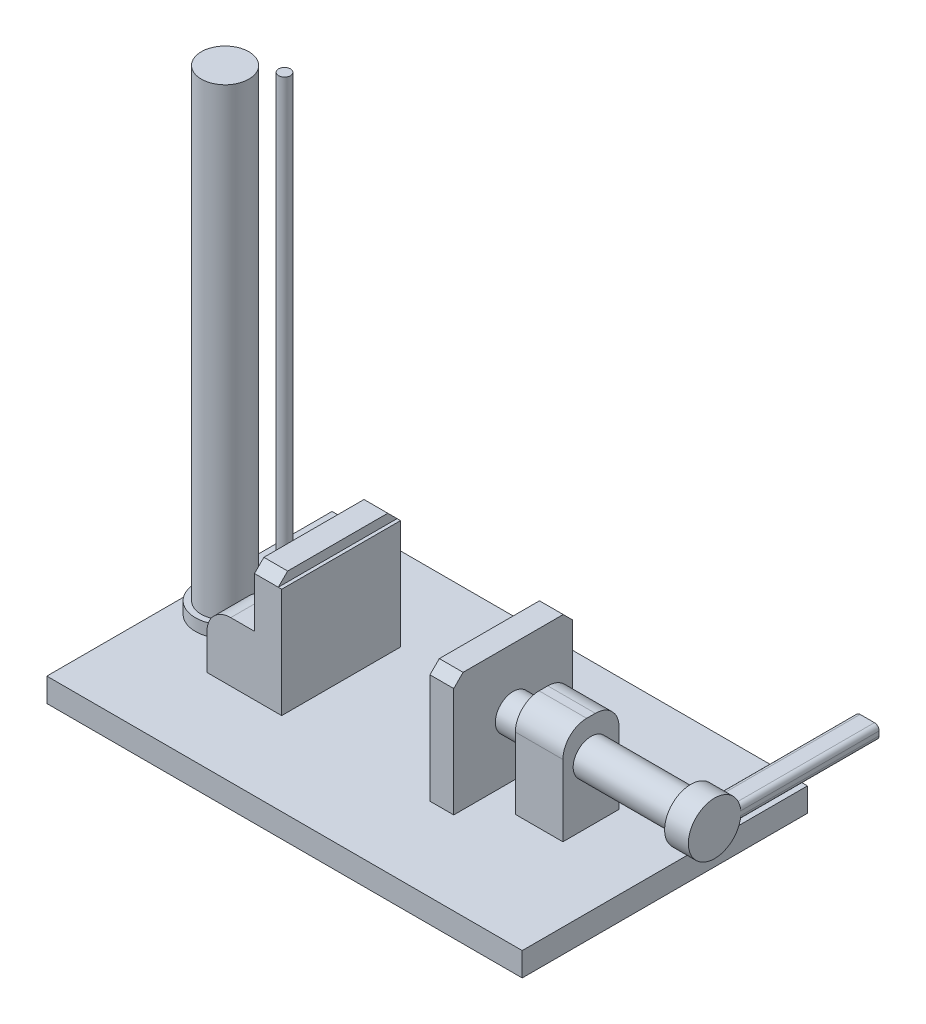
SolidWorks part; units mm, degrees
ref_plane "Front Plane" through (0, 0, 0) normal (0, 0, 1) x (1, 0, 0)
ref_plane "Top Plane" through (0, 0, 0) normal (0, 1, 0) x (1, 0, 0)
ref_plane "Right Plane" through (0, 0, 0) normal (1, 0, 0) x (0, 0, -1)
sketch "Sketch1" plane through (0, 0, 0) normal (0, 1, 0) x (1, 0, 0)
  line L1 (-254, 152.4) -> (254, 152.4)
  line L2 (-254, 152.4) -> (-254, -152.4)
  line L3 (-254, -152.4) -> (254, -152.4)
  line L4 (254, 152.4) -> (254, -152.4)
  line L5 (-254, 152.4) -> (254, -152.4) construction
  line L6 (-254, -152.4) -> (254, 152.4) construction
  point P0 (0, 0)
  dimension "D1" = 508
  dimension "D2" = 304.8
extrude "Boss-Extrude1" add sketch "Sketch1" along normal blind 25.4
sketch "Sketch2" plane through (0, 25.4, 0) normal (0, 1, 0) x (1, 0, 0)
  line L0 (-254, 152.4) -> (-177.8, 152.4)
  line L1 (254, 152.4) -> (-254, 152.4) construction
  line L2 (-215.9, 152.4) -> (-215.9, 25.4)
  line L3 (-254, -152.4) -> (254, -152.4) construction
  line L4 (-215.9, -25.4) -> (-215.9, -152.4)
  circle A0 centre (-215.9, 0) radius 25.4
  line M3 (-254, 152.4) -> (-254, -152.4)
  dimension "D2" = 50.8
  dimension "D1" = 76.2
extrude "Boss-Extrude2" add sketch "Sketch2" along normal blind 508 contours A0 M3 region at (-215.9, 25.4, 0)
sketch "Sketch3" plane through (0, 25.4, 0) normal (0, 1, 0) x (1, 0, 0)
  circle A0 centre (-215.9, 0) radius 31.75
  dimension "D1" = 63.5
extrude "Boss-Extrude3" add sketch "Sketch3" along normal blind 12.7
sketch "Sketch4" plane through (0, 25.4, 0) normal (0, 1, 0) x (1, 0, 0)
  line L0 (-215.9, 0) -> (-152.4, 0)
  circle A0 centre (-152.4, 0) radius 6.35
  dimension "D2" = 12.7
  dimension "D1" = 63.5
extrude "Boss-Extrude4" add sketch "Sketch4" along normal blind 533.4 contours A0 region at (-152.4, 25.4, 6.1704)
sketch "Sketch5" plane through (0, 25.4, 0) normal (0, 1, 0) x (1, 0, 0)
  line L0 (-215.9, 0) -> (-120.9596, 0)
  line L1 (-120.9596, 63.5) -> (-120.9596, -63.5)
  line L2 (-146.3596, 63.5) -> (-95.5596, 63.5)
  line L3 (-146.3596, 63.5) -> (-146.3596, -63.5)
  line L4 (-146.3596, -63.5) -> (-95.5596, -63.5)
  line L5 (-95.5596, 63.5) -> (-95.5596, -63.5)
  line L6 (-146.3596, 63.5) -> (-95.5596, -63.5) construction
  line L7 (-146.3596, -63.5) -> (-95.5596, 63.5) construction
  dimension "D1" = 50.8
  dimension "D2" = 127
extrude "Boss-Extrude5" add sketch "Sketch5" along normal blind 127 contours L5 L2 L1 L4 region at (-108.2596, 25.4, 0)
sketch "Sketch6" plane through (0, 25.4, 0) normal (0, 1, 0) x (1, 0, 0)
  line L1 (-120.9596, 63.5) -> (-171.7596, 63.5)
  line L2 (-120.9596, 63.5) -> (-120.9596, 25.4)
  line L3 (-120.9596, 25.4) -> (-171.7596, 25.4)
  line L4 (-171.7596, 63.5) -> (-171.7596, 25.4)
  line L5 (-120.9596, -63.5) -> (-171.7596, -63.5)
  line L6 (-120.9596, -63.5) -> (-120.9596, -25.4)
  line L7 (-120.9596, -25.4) -> (-171.7596, -25.4)
  line L8 (-171.7596, -63.5) -> (-171.7596, -25.4)
  dimension "D1" = 50.8
  dimension "D2" = 50.8
  dimension "D3" = 38.1
  dimension "D4" = 38.1
extrude "Boss-Extrude6" add sketch "Sketch6" along normal blind 63.5
fillet "Fillet2" radius 25.4 2 edges at (-171.7596, 88.9, -44.45) (-171.7596, 88.9, 44.45)
sketch "Sketch7" plane through (0, 25.4, 0) normal (0, 1, 0) x (1, 0, 0)
  line L0 (-95.5596, 0) -> (254, 0)
  line L1 (-95.5596, 63.5) -> (-95.5596, -63.5) construction
  line L2 (254, -152.4) -> (254, 152.4) construction
  line L4 (66.5202, 63.5) -> (91.9202, 63.5)
  line L5 (66.5202, 63.5) -> (66.5202, -63.5)
  line L6 (66.5202, -63.5) -> (91.9202, -63.5)
  line L7 (91.9202, 63.5) -> (91.9202, -63.5)
  line L8 (66.5202, 63.5) -> (91.9202, -63.5) construction
  line L9 (66.5202, -63.5) -> (91.9202, 63.5) construction
  point P6 (79.2202, 0)
  dimension "D1" = 127
  dimension "D2" = 25.4
extrude "Boss-Extrude7" add sketch "Sketch7" along normal blind 127 contours L7 L6 L5 L4
sketch "Sketch8" plane through (0, 25.4, 0) normal (0, 1, 0) x (1, 0, 0)
  line L1 (124.2964, 30.0313) -> (175.0964, 30.0313)
  line L2 (124.2964, 30.0313) -> (124.2964, -30.0313)
  line L3 (124.2964, -30.0313) -> (175.0964, -30.0313)
  line L4 (175.0964, 30.0313) -> (175.0964, -30.0313)
  line L5 (124.2964, 30.0313) -> (175.0964, -30.0313) construction
  line L6 (124.2964, -30.0313) -> (175.0964, 30.0313) construction
  point P0 (149.6964, 0)
  dimension "D1" = 50.8
  dimension "D2" = 60.0627
extrude "Boss-Extrude9" add sketch "Sketch8" along normal blind 101.6
sketch "Sketch10" plane through (175.0964, 0, 0) normal (1, 0, 0) x (0, 0, -1)
  line L0 (-63.5, 88.9) -> (63.5, 88.9)
  line L1 (-63.5, 152.4) -> (-63.5, 25.4) construction
  line L2 (63.5, 152.4) -> (63.5, 25.4) construction
  circle A0 centre (0, 88.9) radius 19.05
  dimension "D1" = 38.1
extrude "Boss-Extrude10" add sketch "Sketch10" along normal mid plane 213.36 contours L0 A0 | A0 region at (175.0964, 96.9851, 0)
sketch "Sketch11" plane through (281.7764, 0, 0) normal (1, 0, 0) x (0, 0, -1)
  line L0 (19.05, 88.9) -> (145.9979, 88.9)
  line L2 (-10.8194, 96.2269) -> (175.8673, 96.2269)
  line L3 (-10.8194, 96.2269) -> (-10.8194, 81.5731)
  line L4 (-10.8194, 81.5731) -> (175.8673, 81.5731)
  line L5 (175.8673, 96.2269) -> (175.8673, 81.5731)
  line L6 (-10.8194, 96.2269) -> (175.8673, 81.5731) construction
  line L7 (-10.8194, 81.5731) -> (175.8673, 96.2269) construction
  circle A0 centre (0, 88.9) radius 19.05 construction
  circle A1 centre (0, 88.9) radius 19.05 construction
  point P7 (82.5239, 88.9)
extrude "Boss-Extrude11" add sketch "Sketch11" along normal blind 25.4 contours L3 L2 L5 L4
fillet "Fillet4" radius 5.08 4 edges at (307.1764, 81.5731, -82.5239) (281.7764, 81.5731, -96.7259) (307.1764, 96.2269, -82.5239) (281.7764, 96.2269, -96.7259)
sketch "Sketch12" plane through (281.7764, 0, 0) normal (1, 0, 0) x (0, 0, -1)
  line L0 (0, 107.95) -> (0, 69.85)
  circle A0 centre (0, 88.9) radius 19.05 construction
  arc A1 (17.5846, 96.2269) -> (17.5846, 81.5731) centre (0, 88.9) ccw construction
  circle A2 centre (0, 88.9) radius 28.0363
extrude "Boss-Extrude12" add sketch "Sketch12" along normal blind 25.4 contours A2
fillet "Fillet6" radius 25.4 2 edges at (149.6964, 127, -30.0313) (149.6964, 127, 30.0313)
chamfer "Chamfer1" distance 10 angle 45 4 edges at (-108.2596, 152.4, 63.5) (-108.2596, 152.4, -63.5) (79.2202, 152.4, -63.5) (79.2202, 152.4, 63.5)
sketch "Sketch13" plane through (-95.5596, 0, 0) normal (1, 0, 0) x (0, 0, -1)
  line L1 (-63.5, 25.4) -> (63.5, 25.4)
  line L2 (-63.5, 25.4) -> (-63.5, 142.4)
  line L3 (-63.5, 142.4) -> (63.5, 142.4)
  line L4 (63.5, 25.4) -> (63.5, 142.4)
extrude "Boss-Extrude13" add sketch "Sketch13" along normal blind 3.64
